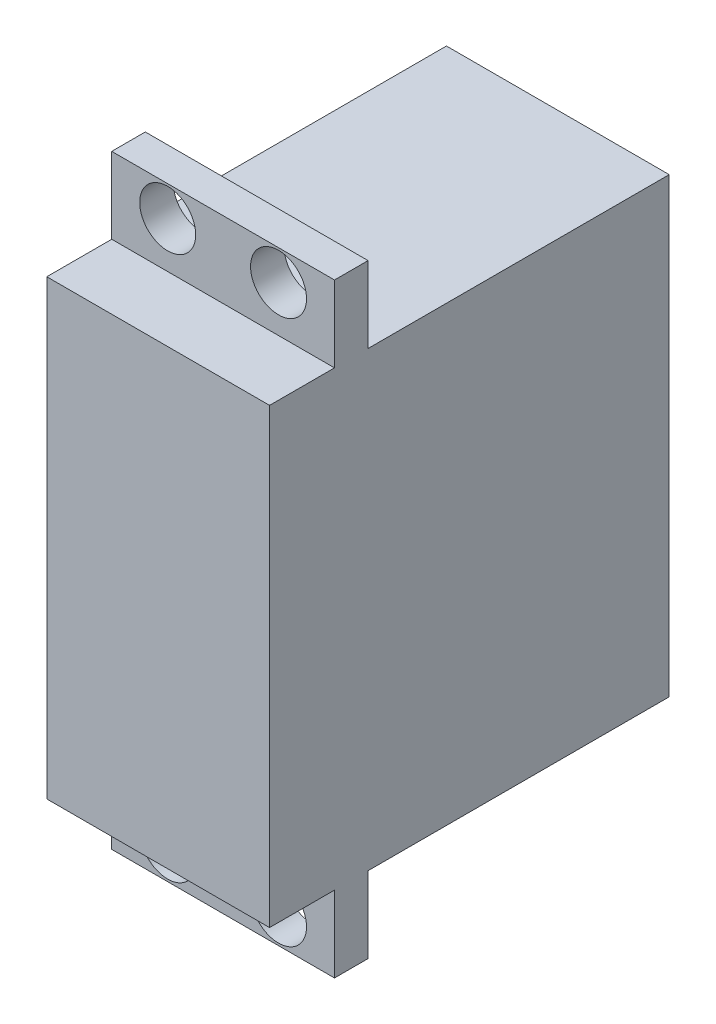
SolidWorks part; units mm, degrees
ref_plane "Front Plane" through (0, 0, 0) normal (0, 0, 1) x (1, 0, 0)
ref_plane "Top Plane" through (0, 0, 0) normal (0, 1, 0) x (1, 0, 0)
ref_plane "Right Plane" through (0, 0, 0) normal (1, 0, 0) x (0, 0, -1)
sketch "Sketch4" plane through (0, 0, 0) normal (0, 0, 1) x (1, 0, 0)
  line L1 (-9.95, -20.2) -> (9.95, -20.2)
  line L2 (-9.95, -20.2) -> (-9.95, 20.2)
  line L3 (-9.95, 20.2) -> (9.95, 20.2)
  line L4 (9.95, -20.2) -> (9.95, 20.2)
  line L5 (-9.95, -20.2) -> (9.95, 20.2) construction
  line L6 (-9.95, 20.2) -> (9.95, -20.2) construction
  point P0 (0, 0)
  dimension "D1" = 40.4
  dimension "D2" = 19.9
extrude "Boss-Extrude3" add sketch "Sketch4" along normal mid plane 35.7
ref_plane "Plane1" through (0, 0, 9.05) normal (0, 0, -1) x (-1, 0, 0)
sketch "Sketch6" plane through (0, 0, 9.05) normal (0, 0, -1) x (-1, 0, 0)
  line L1 (9.95, -27) -> (-9.95, -27)
  line L2 (9.95, -27) -> (9.95, 27)
  line L3 (9.95, 27) -> (-9.95, 27)
  line L4 (-9.95, -27) -> (-9.95, 27)
  line L5 (9.95, -27) -> (-9.95, 27) construction
  line L6 (9.95, 27) -> (-9.95, -27) construction
  point P0 (0, 0)
  dimension "D1" = 19.9
  dimension "D2" = 54
extrude "Boss-Extrude4" add sketch "Sketch6" against normal blind 3
sketch "Sketch1" plane through (0, 0, 0) normal (0, 0, 1) x (1, 0, 0)
  line L0 (0, 0) -> (0, 19.8954) construction
  line L1 (0, 0) -> (16.2753, 0) construction
  circle A0 centre (4.95, -24.3) radius 2.5
  circle A1 centre (-4.95, -24.3) radius 2.5
  circle A2 centre (-4.95, 24.3) radius 2.5
  circle A3 centre (4.95, 24.3) radius 2.5
  dimension "D3" = 9.9
  dimension "D4" = 48.6
  dimension "D1" = 5
extrude "Cut-Extrude2" cut sketch "Sketch1" against normal through all both and the other way through all
ref_plane "Plane2" through (0, 24.3, 0) normal (0, 1, 0) x (1, 0, 0)
ref_plane "Plane3" through (0, 9.3, 0) normal (0, 1, 0) x (1, 0, 0)
ref_axis "Axis1" through (0, 9.3, -19.635) along (0, 0, 1)
